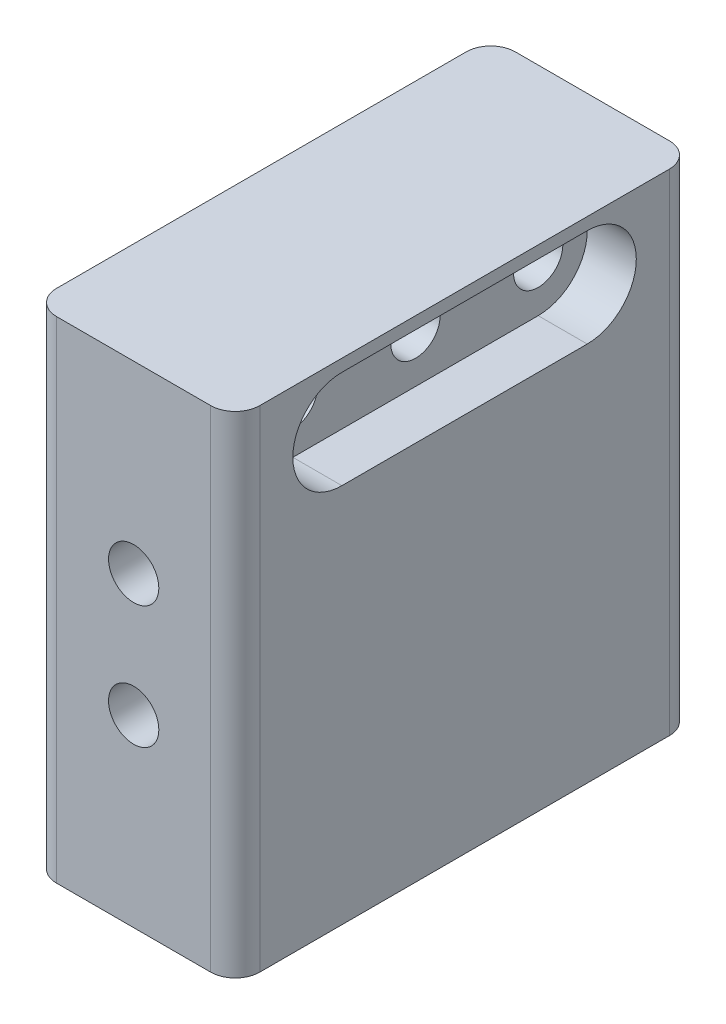
SolidWorks part; units mm, degrees
ref_plane "Front Plane" through (0, 0, 0) normal (0, 0, 1) x (1, 0, 0)
ref_plane "Top Plane" through (0, 0, 0) normal (0, 1, 0) x (1, 0, 0)
ref_plane "Right Plane" through (0, 0, 0) normal (1, 0, 0) x (0, 0, -1)
sketch "Sketch1" plane through (0, 0, 0) normal (0, 1, 0) x (1, 0, 0)
  line L1 (-10.5156, -23.7427) -> (10.5156, -23.7427)
  line L2 (-10.5156, -23.7427) -> (-10.5156, 23.7426)
  line L3 (-10.5156, 23.7426) -> (10.5156, 23.7426)
  line L4 (10.5156, -23.7427) -> (10.5156, 23.7426)
  line L5 (-10.5156, -23.7427) -> (10.5156, 23.7426) construction
  line L6 (-10.5156, 23.7426) -> (10.5156, -23.7427) construction
  point P0 (0, 0)
  dimension "D1" = 21.0312
  dimension "D2" = 47.4853
extrude "Boss-Extrude1" add sketch "Sketch1" along normal mid plane 50.8
sketch "Sketch2" plane through (0, 0, 23.7427) normal (0, 0, 1) x (1, 0, 0)
  line L4 (-10.5156, 25.4) -> (-10.5156, -25.4) construction
  line L5 (-10.5156, 25.4) -> (10.5156, 25.4) construction
  circle A1 centre (0, -6.35) radius 2.6035
  circle A2 centre (0, 6.35) radius 2.6035
  point P7 (0, 0)
  point P9 (0, 0)
  point P10 (-3.4989, 0)
  point P11 (0, 0)
  point P14 (3.8778, 0)
  point P15 (0, 0)
  point P17 (0, 0)
  point P19 (0, 0)
  point P21 (0, 0)
  dimension "D3" = 19.05
  dimension "D1" = 10.5156
  dimension "D2" = 5.207
  dimension "D4" = 12.7
extrude "Cut-Extrude1" cut sketch "Sketch2" against normal through all
sketch "Sketch4" plane through (10.5156, 0, 0) normal (1, 0, 0) x (0, 0, -1)
  line L0 (-23.7427, 25.4) -> (23.7426, 25.4) construction
  circle A0 centre (-12.7, 19.05) radius 2.5527
  circle A1 centre (12.7, 19.05) radius 2.5527
  circle A2 centre (0, 19.05) radius 2.5527
  dimension "D5" = 5.1054
  dimension "D1" = 6.35
  dimension "D3" = 12.7
  dimension "D4" = 12.7
extrude "Cut-Extrude3" cut sketch "Sketch4" against normal through all
fillet "Fillet1" radius 2.54 4 edges at (10.5156, 0, 23.7427) (-10.5156, 0, 23.7427) (-10.5156, 0, -23.7426) (10.5156, 0, -23.7426)
sketch "Sketch7" plane through (10.5156, 0, 0) normal (1, 0, 0) x (0, 0, -1)
  line L0 (-12.7, 19.05) -> (12.7, 19.05) construction
  line L1 (-12.7, 24.13) -> (12.7, 24.13)
  line L2 (-12.7, 13.97) -> (12.7, 13.97)
  arc A0 (-12.7, 24.13) -> (-12.7, 13.97) centre (-12.7, 19.05) ccw
  arc A1 (12.7, 13.97) -> (12.7, 24.13) centre (12.7, 19.05) ccw
  point P4 (0, 19.05)
  dimension "D1" = 5.08
extrude "Cut-Extrude5" cut sketch "Sketch7" against normal blind 5.08
